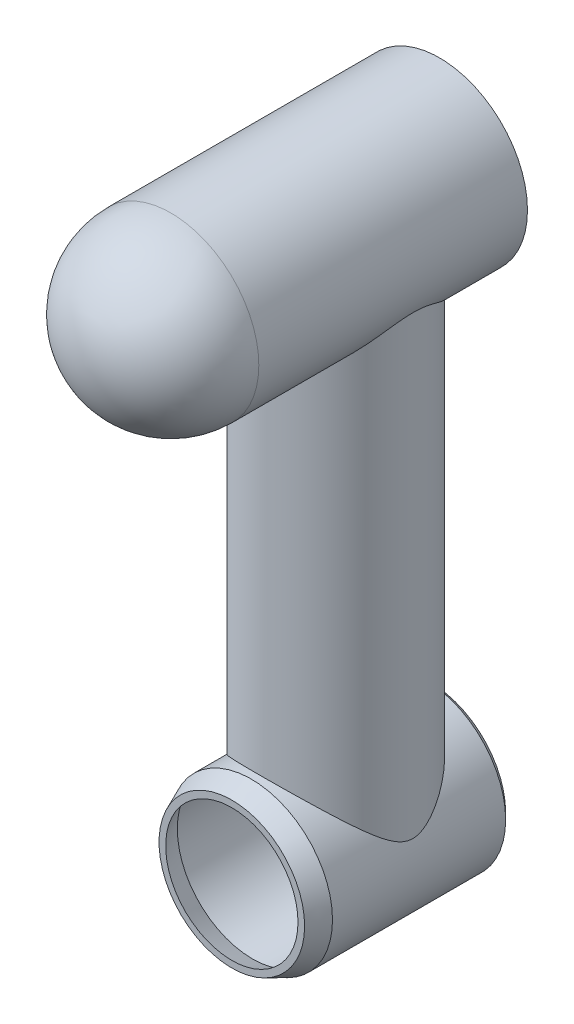
SolidWorks part; units mm, degrees
material "2014-T4"
ref_plane "Front Plane" through (0, 0, 0) normal (0, 0, 1) x (1, 0, 0)
ref_plane "Top Plane" through (0, 0, 0) normal (0, 1, 0) x (1, 0, 0)
ref_plane "Right Plane" through (0, 0, 0) normal (1, 0, 0) x (0, 0, -1)
sketch "Sketch1" plane through (0, 0, 0) normal (0, 0, 1) x (1, 0, 0)
  circle A0 centre (0, 0) radius 72.5
  dimension "D1" = 145
extrude "Boss-Extrude1" add sketch "Sketch1" along normal blind 294
fillet "Fillet1" radius 72.5 1 edges at (72.5, 0, 294)
sketch "Sketch2" plane through (0, 0, 0) normal (0, 1, 0) x (1, 0, 0)
  circle A0 centre (0, -85.5) radius 63.5
  dimension "D2" = 127
  dimension "D1" = 85.5
extrude "Boss-Extrude2" add sketch "Sketch2" against normal blind 431.8
ref_axis "Axis1" through (0, -425.7056, 85.5) along (0, 1, 0)
ref_plane "Plane1" through (0, 0, 85.5) normal (0, 0, 1) x (1, 0, 0)
sketch "Sketch3" plane through (0, 0, 85.5) normal (0, 0, 1) x (1, 0, 0)
  line L0 (-63.5, -431.8) -> (63.5, -431.8) construction
  line L1 (-63.5, -431.8) -> (63.5, -431.8)
  circle A0 centre (0, -431.8) radius 67
  dimension "D1" = 134
extrude "Boss-Extrude3" add sketch "Sketch3" along normal blind 85.75 and the other way blind 78 contours A0
chamfer "Chamfer1" distance 5 angle 45 1 edges at (67, -431.8, 7.5)
chamfer "Chamfer2" distance 16 distance2 7 1 edges at (67, -431.8, 171.25) first distance on face at (67, -431.8, 12.5)
shell "Shell1" thickness 5 removed face at (60, -431.8, 171.25) removed face at (72.5, 0, 0)
